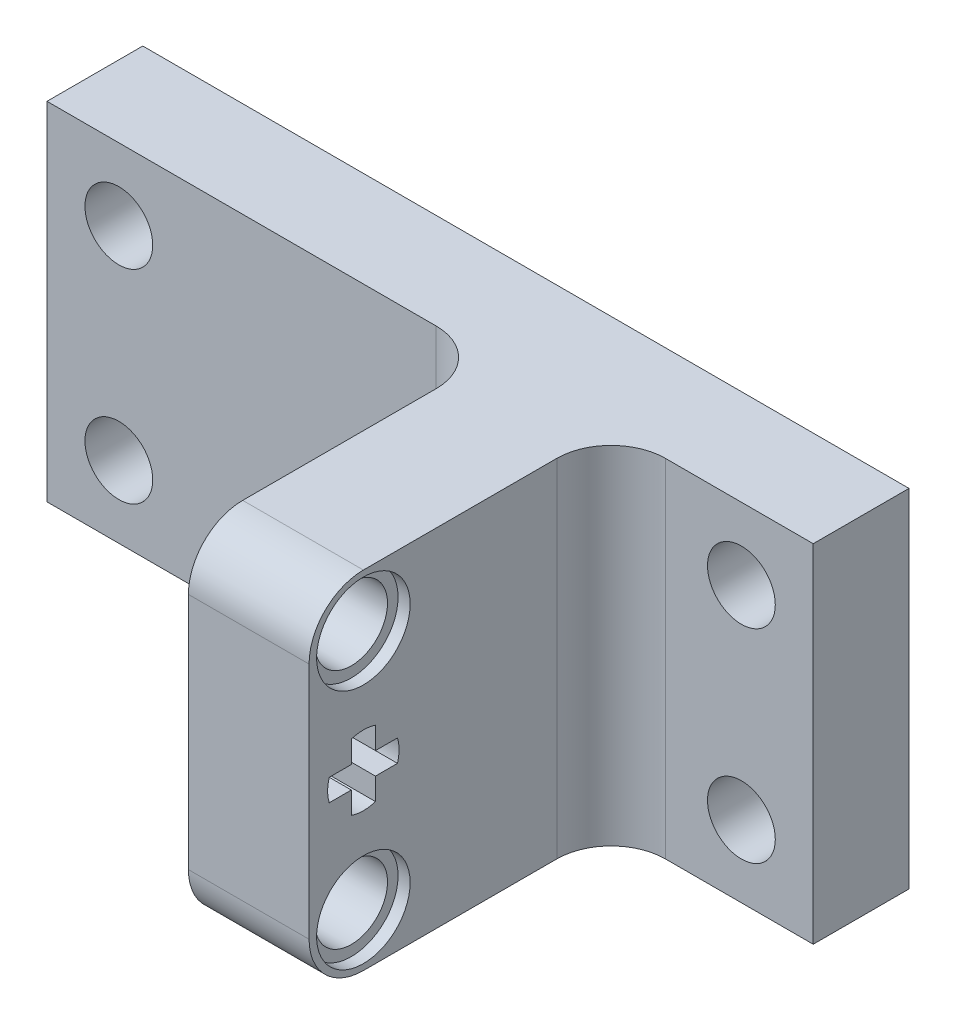
SolidWorks part; units mm, degrees
ref_plane "Front Plane" through (0, 0, 0) normal (0, 0, 1) x (1, 0, 0)
ref_plane "Top Plane" through (0, 0, 0) normal (0, 1, 0) x (1, 0, 0)
ref_plane "Right Plane" through (0, 0, 0) normal (1, 0, 0) x (0, 0, -1)
sketch "Sketch2" plane through (0, 0, 0) normal (0, 1, 0) x (1, 0, 0)
  line L0 (4, -3.175) -> (4, -19.6)
  line L1 (-25.4, 3.175) -> (25.4, 3.175)
  line L2 (-25.4, 3.175) -> (-25.4, -3.175)
  line L3 (-25.4, -3.175) -> (4, -3.175)
  line L4 (25.4, 3.175) -> (25.4, -3.175)
  line L5 (-25.4, 3.175) -> (25.4, -3.175) construction
  line L6 (-25.4, -3.175) -> (25.4, 3.175) construction
  line L8 (12, -19.6) -> (12, -3.175)
  line L9 (12, -3.175) -> (25.4, -3.175)
  line L10 (4, -19.6) -> (4, -23.2)
  line L11 (4, -23.2) -> (12, -23.2)
  line L12 (12, -23.2) -> (12, -19.6)
  point P0 (0, 0)
  dimension "D1" = 50.8
  dimension "D2" = 22.775
  dimension "D3" = 8
  dimension "D4" = 3.6
  dimension "D5" = 6.35
  dimension "D6" = 21.4
extrude "Boss-Extrude1" add sketch "Sketch2" along normal mid plane 23
sketch "Sketch3" plane through (12, 0, 0) normal (1, 0, 0) x (0, 0, -1)
  line L0 (-20.4, 0.7314) -> (-20.4, 2.1941)
  line L1 (-18.8, 2.1941) -> (-18.8, 0.7314)
  line L2 (-20.4, 0.7314) -> (-18.8, 0.7314) construction
  line L3 (-20.4, 0.7314) -> (-20.4, -0.7314) construction
  line L4 (-20.4, 0.7314) -> (-21.8627, 0.7314)
  line L5 (-21.8627, -0.7314) -> (-20.4, -0.7314)
  line L6 (-20.4, -0.7314) -> (-20.4, -2.1941)
  line L7 (-18.8, -2.1941) -> (-18.8, -0.7314)
  line L8 (-18.8, -0.7314) -> (-17.3373, -0.7314)
  line L9 (-18.8, 0.7314) -> (-17.3373, 0.7314)
  line L10 (-17.3373, 0.7314) -> (-15.4007, 0.7314)
  line L11 (-23.2, 11.5) -> (-23.2, -11.5) construction
  circle A0 centre (-19.6, 0) radius 2.5157 construction
  circle A1 centre (-19.6, 8) radius 3.1
  circle A2 centre (-19.6, -8) radius 3.1
  circle A3 centre (-19.6, 8) radius 2.4
  circle A4 centre (-19.6, -8) radius 2.4
  arc A5 (-20.4, 2.1941) -> (-18.8, 2.1941) centre (-19.6, -0.2798) cw
  arc A6 (-21.8627, 0.7314) -> (-21.8627, -0.7314) centre (-19.3677, 0) ccw
  arc A7 (-20.4, -2.1941) -> (-18.8, -2.1941) centre (-19.6, 0.2798) ccw
  arc A8 (-17.3373, 0.7314) -> (-17.3373, -0.7314) centre (-19.8323, 0) cw
  point P12 (-19.6, 0.7314)
  point P26 (-21.9677, 0)
  point P27 (-19.6, -2.3202)
  dimension "D1" = 6.2
  dimension "D2" = 4.8
  dimension "D7" = 2.6
  dimension "D3" = 8
  dimension "D4" = 8
  dimension "D5" = 1.4627
  dimension "D6" = 1.6
  dimension "D8" = 3.6
extrude "Cut-Extrude1" cut sketch "Sketch3" against normal through all contours A3 | A8 L9 L1 A5 L0 L4 A6 L5 L6 A7 L7 L8 | A4 region at (12, 0, 19.6) region at (12, 8, 19.6) region at (12, -8, 19.6)
extrude "Cut-Extrude2" cut sketch "Sketch3<3>" against normal blind 0.8 contours A1 A3 | A2 A4 region at (12, 8, 22.6123) region at (12, -8, 22.6123)
sketch "Sketch3<3>" plane through (12, 0, 0) normal (1, 0, 0) x (0, 0, -1) same geometry as "Sketch3"
ref_plane "Plane1" through (8, 0, 0) normal (1, 0, 0) x (0, 0, -1)
mirror "Mirror1" about plane through (8, 0, 0) normal (1, 0, 0) of "Cut-Extrude2"
fillet "Fillet1" radius 3.6 4 edges at (8, -11.5, 23.2) (8, 11.5, 23.2) (4, 0, 3.175) (12, 0, 3.175)
hole_wizard "#8 Clearance Hole1" positions "Sketch4" profile "Sketch5" hole size "#8" standard "ANSI Inch" end condition through all
sketch "Sketch4" plane through (0, 0, 3.175) normal (0, 0, 1) x (1, 0, 0)
  line L0 (-25.4, 11.5) -> (0.4, 11.5) construction
  line L1 (-25.4, 11.5) -> (-25.4, -11.5) construction
  line L2 (25.4, 11.5) -> (25.4, -11.5) construction
  line L3 (15.6, -11.5) -> (25.4, -11.5) construction
  point P0 (-20.6375, 6.7375)
  point P2 (-20.6375, -6.7375)
  point P4 (20.6375, -6.7375)
  point P6 (20.6375, 6.7375)
  point P8 (0, 0)
  point P9 (0, 0)
  point P10 (0, 0)
  point P11 (0, 0)
  point P22 (20.6375, 6.7375)
  dimension "D1" = 4.7625
  dimension "D2" = 4.7625
  dimension "D3" = 4.7625
  dimension "D4" = 4.7625
sketch "Sketch5" plane through (-20.6375, 6.7375, 3.175) normal (1, 0, 0) x (0, -1, 0)
  line L0 (0, 0) -> (0, 6.35)
  line L1 (0, 6.35) -> (2.2479, 6.35)
  line L2 (2.2479, 6.35) -> (2.2479, 0)
  line L5 (2.2479, 0) -> (0, 0)
  line L11 (0, -6.35) -> (0, 107.95) construction
  dimension "Thru Hole Dia." = 4.4958
  dimension "Thru Hole Depth" = 6.35
